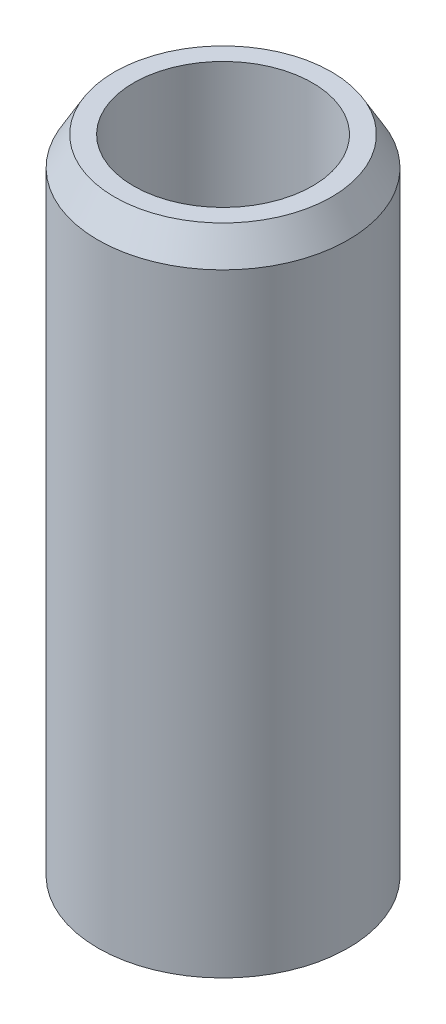
SolidWorks part; units mm, degrees
ref_plane "Front Plane" through (0, 0, 0) normal (0, 0, 1) x (1, 0, 0)
ref_plane "Top Plane" through (0, 0, 0) normal (0, 1, 0) x (1, 0, 0)
ref_plane "Right Plane" through (0, 0, 0) normal (1, 0, 0) x (0, 0, -1)
sketch "Sketch1" plane through (0, 0, 0) normal (0, 1, 0) x (1, 0, 0)
  circle A0 centre (0, 0) radius 25
  dimension "SHAFT_OD" = 50
extrude "Boss-Extrude1" add sketch "Sketch1" along normal blind 131.6077
sketch "Sketch2" plane through (0, 0, 0) normal (0, 1, 0) x (1, 0, 0)
  circle A0 centre (0, 0) radius 17.8701
  dimension "BORE_D" = 35.7402
extrude "Cut-Extrude1" cut sketch "Sketch2" along normal through all
chamfer "Chamfer1" distance 5.7639 angle 30 2 edges at (0, 131.6077, 25) (0, 0, 25) first distance on face at (0, 131.6077, 25) first distance on face at (0, 0, 17.8701)
